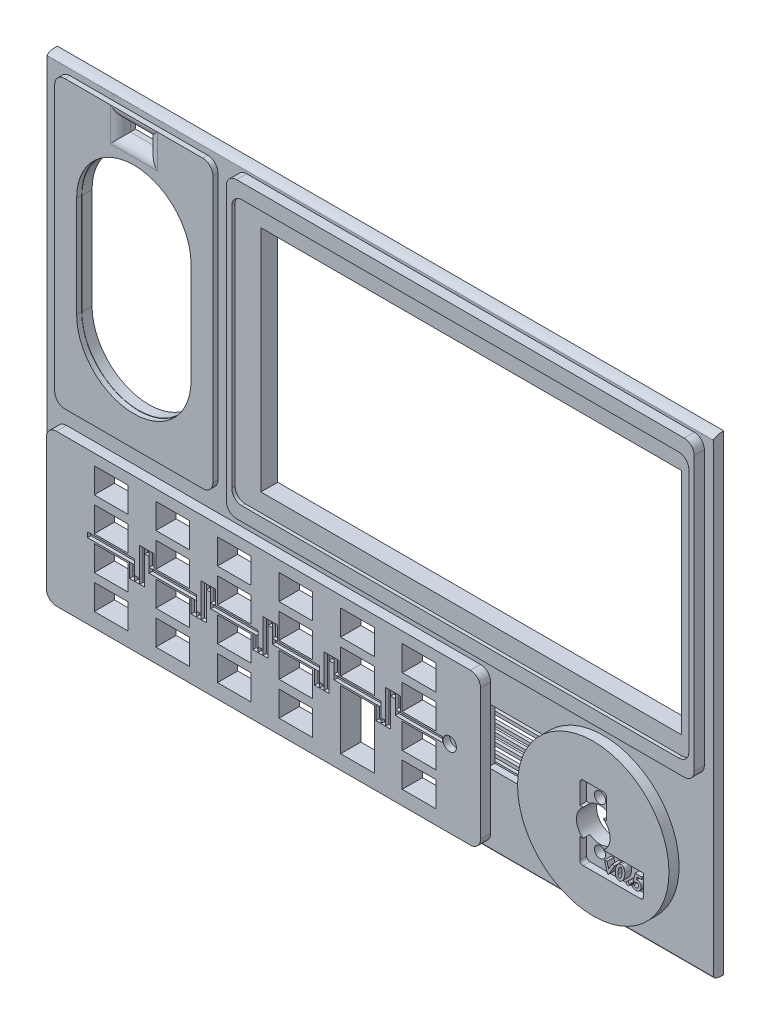
SolidWorks part; units mm, degrees
ref_plane "Front Plane" through (0, 0, 0) normal (0, 0, 1) x (1, 0, 0)
ref_plane "Top Plane" through (0, 0, 0) normal (0, 1, 0) x (1, 0, 0)
ref_plane "Right Plane" through (0, 0, 0) normal (1, 0, 0) x (0, 0, -1)
sketch "Sketch1" plane through (0, 0, 0) normal (0, 0, 1) x (1, 0, 0)
  line L1 (99, -70) -> (-99, -70)
  line L2 (99, -70) -> (99, 70)
  line L3 (99, 70) -> (-99, 70)
  line L4 (-99, -70) -> (-99, 70)
  line L5 (99, -70) -> (-99, 70) construction
  line L6 (99, 70) -> (-99, -70) construction
  point P0 (0, 0)
  dimension "D1" = 198
  dimension "D2" = 140
extrude "main_body" add sketch "Sketch1" along normal blind 3
fillet "long_corners" radius 3 2 edges at (0, 70, 3) (0, -70, 3) second distance 1 first distance on face at (0, 70, 1.5) first distance on face at (0, -70, 1.5)
sketch "Sketch2" plane through (0, 0, 3) normal (0, 0, 1) x (1, 0, 0)
  line L0 (-99, 24.75) -> (99, 24.75) construction
  line L1 (-99, 69) -> (-99, -69) construction
  line L2 (99, -69) -> (99, 69) construction
  line L3 (99, 69) -> (-99, 69) construction
  line L4 (-48.25, -17.75) -> (-95.25, -17.75)
  line L5 (-48.25, -17.75) -> (-48.25, 67.25)
  line L6 (-48.25, 67.25) -> (-95.25, 67.25)
  line L7 (-95.25, -17.75) -> (-95.25, 67.25)
  line L8 (-48.25, -17.75) -> (-95.25, 67.25) construction
  line L9 (-48.25, 67.25) -> (-95.25, -17.75) construction
  point P6 (-71.75, 24.75)
  dimension "D1" = 85
  dimension "D2" = 47
  dimension "D3" = 27.25
  dimension "D4" = 44.25
extrude "speaker" add sketch "Sketch2" along normal blind 1.5
fillet "speaker_corners" radius 3 4 edges at (-95.25, 67.25, 3.75) (-95.25, -17.75, 3.75) (-48.25, -17.75, 3.75) (-48.25, 67.25, 3.75)
sketch "Sketch19" plane through (0, 0, 4.5) normal (0, 0, 1) x (1, 0, 0)
  line L0 (-71.75, 67.25) -> (-71.75, -17.75) construction
  line L1 (-51.25, 67.25) -> (-92.25, 67.25) construction
  line L2 (-92.25, -17.75) -> (-51.25, -17.75) construction
  line L3 (-71.75, 8.25) -> (-71.75, 38.25) construction
  line L4 (-95.25, 64.25) -> (-95.25, -14.75) construction
  line L5 (-95.25, 24.75) -> (-48.25, 24.75) construction
  line L6 (-48.25, -14.75) -> (-48.25, 64.25) construction
  line L7 (-88.75, 8.25) -> (-88.75, 38.25)
  line L8 (-54.75, 8.25) -> (-54.75, 38.25)
  arc A0 (-88.75, 8.25) -> (-54.75, 8.25) centre (-71.75, 8.25) ccw
  arc A1 (-54.75, 38.25) -> (-88.75, 38.25) centre (-71.75, 38.25) ccw
  point P14 (-71.75, 23.25)
  point P19 (-71.75, -8.75)
  point P20 (-71.75, 55.25)
  dimension "D2" = 64
  dimension "D1" = 34
  dimension "D3" = 12
extrude "speaker_cut" cut sketch "Sketch19" against normal through all
sketch "Sketch21" plane through (0, 0, 0) normal (0, 0, -1) x (-1, 0, 0)
  line L0 (71.75, -8.75) -> (71.75, 55.25) construction
  line L2 (54.75, 8.25) -> (54.75, 38.25) construction
  line L3 (54.75, 23.25) -> (88.75, 23.25) construction
  line L4 (88.75, 38.25) -> (88.75, 8.25) construction
  line L5 (50.25, 59.25) -> (93.25, 59.25)
  line L6 (50.25, 59.25) -> (50.25, -12.75)
  line L7 (50.25, -12.75) -> (93.25, -12.75)
  line L8 (93.25, 59.25) -> (93.25, -12.75)
  line L9 (50.25, 59.25) -> (93.25, -12.75) construction
  line L10 (50.25, -12.75) -> (93.25, 59.25) construction
  arc A0 (54.75, 8.25) -> (88.75, 8.25) centre (71.75, 8.25) ccw construction
  arc A1 (88.75, 38.25) -> (54.75, 38.25) centre (71.75, 38.25) ccw construction
  point P14 (71.75, 23.25)
  dimension "D1" = 43
  dimension "D2" = 72
extrude "speaker_slot" cut sketch "Sketch21" against normal blind 3
sketch "Sketch36" plane through (0, 0, 3) normal (0, 0, -1) x (-1, 0, 0)
  line L0 (50.25, 23.25) -> (93.25, 23.25) construction
  line L1 (50.25, 59.25) -> (50.25, -12.75) construction
  line L2 (71.75, 8.2639) -> (71.75, 38.2361) construction
  line L3 (71.75, 8.2639) -> (71.75, 38.2361) construction
  line L4 (93.25, -12.75) -> (93.25, 59.25) construction
  line L5 (50.25, 59.25) -> (50.25, -12.75) construction
  line L6 (54.8316, 8.2639) -> (54.8316, 38.2361)
  line L9 (88.6684, 8.2639) -> (88.6684, 38.2361)
  line L10 (54.25, 8.2639) -> (54.25, 38.2361)
  line L11 (89.25, 8.2639) -> (89.25, 38.2361)
  line L12 (93.25, 59.25) -> (50.25, 59.25) construction
  line L13 (71.75, 59.25) -> (71.75, -12.75) construction
  line L14 (50.25, -12.75) -> (93.25, -12.75) construction
  line L23 (50.25, 57.25) -> (93.25, 57.25)
  line L25 (50.25, 57.25) -> (50.25, 56.75)
  line L26 (93.25, -0.25) -> (87.75, -0.25)
  line L27 (50.25, 56.75) -> (93.25, 56.75)
  line L28 (93.25, 57.25) -> (93.25, 56.75)
  line L37 (93.25, -12.75) -> (93.25, 59.25) construction
  line L38 (93.25, -0.25) -> (93.25, 0.25)
  line L39 (93.25, 0.25) -> (87.75, 0.25)
  line L48 (93.25, -10.75) -> (50.25, -10.75)
  line L49 (93.25, -10.75) -> (93.25, -10.25)
  line L50 (93.25, -10.25) -> (50.25, -10.25)
  line L51 (50.25, -10.75) -> (50.25, -10.25)
  line L52 (93.25, 46.75) -> (87.75, 46.75)
  line L53 (93.25, 46.75) -> (93.25, 46.25)
  line L54 (93.25, 46.25) -> (87.75, 46.25)
  line L55 (87.75, 46.75) -> (87.75, 46.25)
  line L56 (93.25, 35.25) -> (89.75, 35.25)
  line L57 (93.25, 35.25) -> (93.25, 34.75)
  line L58 (93.25, 34.75) -> (89.75, 34.75)
  line L59 (89.75, 35.25) -> (89.75, 34.75)
  line L60 (93.25, 23.25) -> (89.75, 23.25)
  line L61 (93.25, 23.25) -> (93.25, 23.75)
  line L62 (93.25, 23.75) -> (89.75, 23.75)
  line L63 (89.75, 23.25) -> (89.75, 23.75)
  line L64 (93.25, 10.75) -> (89.75, 10.75)
  line L65 (93.25, 10.75) -> (93.25, 11.25)
  line L66 (93.25, 11.25) -> (89.75, 11.25)
  line L67 (89.75, 10.75) -> (89.75, 11.25)
  line L68 (87.75, -0.25) -> (87.75, 0.25)
  line L69 (93.25, -5.25) -> (83.25, -5.25)
  line L70 (93.25, -5.25) -> (93.25, -5.75)
  line L71 (93.25, -5.75) -> (83.25, -5.75)
  line L72 (83.25, -5.25) -> (83.25, -5.75)
  line L73 (93.25, 52.25) -> (83.25, 52.25)
  line L74 (93.25, 52.25) -> (93.25, 51.75)
  line L75 (93.25, 51.75) -> (83.25, 51.75)
  line L76 (83.25, 52.25) -> (83.25, 51.75)
  line L77 (50.25, 52.25) -> (60.25, 52.25)
  line L78 (50.25, 52.25) -> (50.25, 51.75)
  line L79 (50.25, 51.75) -> (60.25, 51.75)
  line L80 (60.25, 52.25) -> (60.25, 51.75)
  line L81 (50.25, 46.75) -> (55.75, 46.75)
  line L82 (50.25, 46.75) -> (50.25, 46.25)
  line L83 (50.25, 46.25) -> (55.75, 46.25)
  line L84 (55.75, 46.75) -> (55.75, 46.25)
  line L85 (50.25, 35.25) -> (53.75, 35.25)
  line L86 (50.25, 35.25) -> (50.25, 34.75)
  line L87 (50.25, 34.75) -> (53.75, 34.75)
  line L88 (53.75, 35.25) -> (53.75, 34.75)
  line L89 (50.25, 23.25) -> (53.75, 23.25)
  line L90 (50.25, 23.25) -> (50.25, 23.75)
  line L91 (50.25, 23.75) -> (53.75, 23.75)
  line L92 (53.75, 23.25) -> (53.75, 23.75)
  line L93 (50.25, 10.25) -> (53.75, 10.25)
  line L94 (50.25, 10.25) -> (50.25, 10.75)
  line L95 (50.25, 10.75) -> (53.75, 10.75)
  line L96 (53.75, 10.25) -> (53.75, 10.75)
  line L97 (50.25, -0.25) -> (55.75, -0.25)
  line L98 (50.25, -0.25) -> (50.25, 0.25)
  line L99 (50.25, 0.25) -> (55.75, 0.25)
  line L100 (55.75, -0.25) -> (55.75, 0.25)
  line L101 (50.25, -5.25) -> (60.25, -5.25)
  line L102 (50.25, -5.25) -> (50.25, -5.75)
  line L103 (50.25, -5.75) -> (60.25, -5.75)
  line L104 (60.25, -5.25) -> (60.25, -5.75)
  arc A0 (54.25, 8.2639) -> (89.25, 8.2639) centre (71.75, 8.2639) ccw
  arc A1 (89.25, 38.2361) -> (54.25, 38.2361) centre (71.75, 38.2361) ccw
  arc A4 (54.8316, 8.2639) -> (88.6684, 8.2639) centre (71.75, 8.2639) ccw
  arc A5 (88.6684, 38.2361) -> (54.8316, 38.2361) centre (71.75, 38.2361) ccw
  point P6 (71.75, 23.25)
  point P22 (71.75, 23.25)
  point P31 (89.25, 23.25)
  point P32 (71.75, 55.1546)
  point P33 (71.75, -8.6546)
  point P95 (52, 35.25)
  point P96 (55.25, 51.75)
  point P97 (91.5, 10.75)
  dimension "D48" = 0.5816
  dimension "D1" = 33.8368
  dimension "D2" = 35
  dimension "D3" = 63.8091
  dimension "D4" = 0.5
  dimension "D5" = 0.5
  dimension "D6" = 0.5
  dimension "D7" = 0.5
  dimension "D8" = 0.5
  dimension "D9" = 11
  dimension "D10" = 11
  dimension "D11" = 5
  dimension "D12" = 4.5
  dimension "D13" = 10
  dimension "D14" = 5.5
  dimension "D15" = 3.5
  dimension "D16" = 3.5
  dimension "D17" = 0.5
  dimension "D18" = 0.5
  dimension "D19" = 0.5
  dimension "D20" = 0.5
  dimension "D21" = 11
  dimension "D22" = 11
  dimension "D23" = 5
  dimension "D24" = 10
  dimension "D25" = 5.5
  dimension "D26" = 3.5
  dimension "D27" = 3.5
  dimension "D28" = 0.5
  dimension "D29" = 0.5
  dimension "D30" = 0.5
  dimension "D31" = 0.5
  dimension "D32" = 0.5
  dimension "D33" = 0.5
  dimension "D34" = 0.5
  dimension "D35" = 12
  dimension "D36" = 10.5
  dimension "D37" = 5.5
  dimension "D38" = 5
  dimension "D39" = 4.5
  dimension "D40" = 3.5
  dimension "D41" = 10
  dimension "D42" = 4.5
  dimension "D43" = 5
  dimension "D44" = 10
  dimension "D45" = 3.5
  dimension "D46" = 5.5
  dimension "D47" = 10
extrude "speaker_print_support" add sketch "Sketch36" along normal blind 3
sketch "Sketch3" plane through (0, 0, 3) normal (0, 0, 1) x (1, 0, 0)
  line L0 (-99, 24.625) -> (99, 24.625) construction
  line L1 (-99, 69) -> (-99, -69) construction
  line L2 (99, -69) -> (99, 69) construction
  line L4 (-48.25, -14.75) -> (-48.25, 64.25) construction
  line L5 (96.25, -19) -> (-42.75, -19)
  line L6 (96.25, -19) -> (96.25, 68.25)
  line L7 (96.25, 68.25) -> (-42.75, 68.25)
  line L8 (-42.75, -19) -> (-42.75, 68.25)
  line L9 (96.25, -19) -> (-42.75, 68.25) construction
  line L10 (96.25, 68.25) -> (-42.75, -19) construction
  line L11 (99, 70) -> (-99, 70) construction
  point P8 (26.75, 24.625)
  dimension "D1" = 1.75
  dimension "D2" = 87.25
  dimension "D3" = 139
  dimension "D4" = 2.75
  dimension "D5" = 5.5
extrude "lcd" add sketch "Sketch3" along normal blind 3
fillet "lcd_corners" radius 3 4 edges at (96.25, -19, 4.5) (-42.75, -19, 4.5) (96.25, 68.25, 4.5) (-42.75, 68.25, 4.5)
sketch "Sketch9" plane through (0, 0, 6) normal (0, 0, 1) x (1, 0, 0)
  line L0 (-42.75, 24.5) -> (96.25, 24.5) construction
  line L1 (-42.75, 65.25) -> (-42.75, -16) construction
  line L2 (96.25, -16) -> (96.25, 65.25) construction
  line L3 (-39.75, -19) -> (93.25, -19) construction
  line L4 (94.65, -14.875) -> (-41.15, -14.875)
  line L5 (94.65, -14.875) -> (94.65, 63.875)
  line L6 (94.65, 63.875) -> (-41.15, 63.875)
  line L7 (-41.15, -14.875) -> (-41.15, 63.875)
  line L8 (94.65, -14.875) -> (-41.15, 63.875) construction
  line L9 (94.65, 63.875) -> (-41.15, -14.875) construction
  line L10 (93.25, 68.25) -> (-39.75, 68.25) construction
  line L11 (96.25, -16) -> (96.25, 65.25) construction
  point P6 (26.75, 24.5)
  dimension "D1" = 135.8
  dimension "D2" = 78.75
  dimension "D3" = 1.6
  dimension "D4" = 4.125
  dimension "D5" = 4.375
  dimension "D6" = 1.6
extrude "lcd_front" cut sketch "Sketch9" against normal blind 1
fillet "lcd_front_corners" radius 3 4 edges at (94.65, -14.875, 5.5) (94.65, 63.875, 5.5) (-41.15, 63.875, 5.5) (-41.15, -14.875, 5.5)
sketch "Sketch10" plane through (0, 0, 0) normal (0, 0, -1) x (-1, 0, 0)
  line L0 (-94.65, -11.875) -> (-94.65, 60.875) construction
  line L1 (-91.65, 63.875) -> (38.15, 63.875) construction
  line L2 (41.15, 63.875) -> (41.15, -14.875) construction
  line L3 (-94.65, 63.875) -> (41.15, 63.875) construction
  line L4 (33.5, -9.5) -> (-91.5, -9.5)
  line L5 (33.5, -9.5) -> (33.5, 58.5)
  line L6 (33.5, 58.5) -> (-91.5, 58.5)
  line L7 (-91.5, -9.5) -> (-91.5, 58.5)
  line L8 (-91.5, -9.5) -> (33.5, 58.5) construction
  line L9 (-91.5, 58.5) -> (33.5, -9.5) construction
  line L10 (-99, -70) -> (-99, 70) construction
  line L11 (-99, 70) -> (99, 70) construction
  line L13 (38.15, -14.875) -> (-91.65, -14.875) construction
  dimension "D1" = 125
  dimension "D2" = 68
  dimension "D3" = 7.5
  dimension "D4" = 7.65
  dimension "D5" = 11.5
  dimension "D6" = 5.375
  dimension "D7" = 3.15
  dimension "D8" = 5.375
  dimension "D9" = 5.375
extrude "lcd_back" cut sketch "Sketch10" against normal through all
sketch "Sketch4" plane through (0, 0, 3) normal (0, 0, 1) x (1, 0, 0)
  line L0 (-99, -45.75) -> (99, -45.75) construction
  line L1 (-99, 69) -> (-99, -69) construction
  line L2 (99, -69) -> (99, 69) construction
  line L4 (-92.25, -17.75) -> (-51.25, -17.75) construction
  line L5 (32.75, -68.25) -> (-96.25, -68.25)
  line L6 (32.75, -68.25) -> (32.75, -23.25)
  line L7 (32.75, -23.25) -> (-96.25, -23.25)
  line L8 (-96.25, -68.25) -> (-96.25, -23.25)
  line L9 (32.75, -68.25) -> (-96.25, -23.25) construction
  line L10 (32.75, -23.25) -> (-96.25, -68.25) construction
  line L11 (-99, -70) -> (99, -70) construction
  point P8 (-31.75, -45.75)
  dimension "D1" = 1.75
  dimension "D2" = 129
  dimension "D3" = 45
  dimension "D4" = 2.75
  dimension "D5" = 5.5
extrude "keypad" add sketch "Sketch4" along normal blind 3
fillet "keypad_corners" radius 3 4 edges at (-96.25, -68.25, 4.5) (32.75, -68.25, 4.5) (32.75, -23.25, 4.5) (-96.25, -23.25, 4.5)
sketch "Sketch25" plane through (0, 0, 6) normal (0, 0, 1) x (1, 0, 0)
  line L0 (-96.25, -30.25) -> (32.75, -30.25) construction
  line L1 (29.75, -23.25) -> (-93.25, -23.25) construction
  line L2 (-93.25, -68.25) -> (29.75, -68.25) construction
  line L3 (-77, -23.25) -> (-77, -68.25) construction
  line L5 (-35.4, -64) -> (32.75, -64) construction
  line L6 (-96.25, -26.25) -> (-96.25, -65.25) construction
  line L11 (32.75, -65.25) -> (32.75, -26.25) construction
  line L12 (-58.7, -23.25) -> (-58.7, -68.25) construction
  line L13 (-96.25, -40.25) -> (32.75, -40.25) construction
  line L14 (29.75, -23.25) -> (-93.25, -23.25) construction
  line L15 (-40.4, -23.25) -> (-40.4, -68.25) construction
  line L16 (-93.25, -68.25) -> (29.75, -68.25) construction
  line L17 (-72, -34) -> (-82, -34)
  line L18 (-22.1, -23.25) -> (-22.1, -68.25) construction
  line L19 (-96.25, -50.25) -> (32.75, -50.25) construction
  line L20 (-3.8, -23.25) -> (-3.8, -68.25) construction
  line L21 (-72, -34) -> (-72, -26.5)
  line L22 (14.5, -23.25) -> (14.5, -68.25) construction
  line L23 (-96.25, -26.25) -> (-96.25, -65.25) construction
  line L24 (-96.25, -60.25) -> (32.75, -60.25) construction
  line L25 (-72, -26.5) -> (-82, -26.5)
  line L26 (-82, -34) -> (-82, -26.5)
  line L27 (-72, -34) -> (-82, -26.5) construction
  line L28 (-72, -26.5) -> (-82, -34) construction
  line L29 (-72, -44) -> (-82, -44)
  line L30 (-72, -44) -> (-72, -36.5)
  line L31 (-72, -36.5) -> (-82, -36.5)
  line L32 (-82, -44) -> (-82, -36.5)
  line L33 (-72, -44) -> (-82, -36.5) construction
  line L34 (-72, -36.5) -> (-82, -44) construction
  line L35 (-72, -54) -> (-82, -54)
  line L36 (-72, -54) -> (-72, -46.5)
  line L37 (-72, -46.5) -> (-82, -46.5)
  line L38 (-82, -54) -> (-82, -46.5)
  line L39 (-72, -54) -> (-82, -46.5) construction
  line L40 (-72, -46.5) -> (-82, -54) construction
  line L41 (-72, -64) -> (-82, -64)
  line L42 (-72, -64) -> (-72, -56.5)
  line L43 (-72, -56.5) -> (-82, -56.5)
  line L44 (-82, -64) -> (-82, -56.5)
  line L45 (-72, -64) -> (-82, -56.5) construction
  line L46 (-72, -56.5) -> (-82, -64) construction
  line L47 (-53.7, -34) -> (-63.7, -34)
  line L48 (-53.7, -34) -> (-53.7, -26.5)
  line L49 (-53.7, -26.5) -> (-63.7, -26.5)
  line L50 (-63.7, -34) -> (-63.7, -26.5)
  line L51 (-53.7, -34) -> (-63.7, -26.5) construction
  line L52 (-53.7, -26.5) -> (-63.7, -34) construction
  line L53 (-53.7, -44) -> (-63.7, -44)
  line L54 (-53.7, -44) -> (-53.7, -36.5)
  line L55 (-53.7, -36.5) -> (-63.7, -36.5)
  line L56 (-63.7, -44) -> (-63.7, -36.5)
  line L57 (-53.7, -44) -> (-63.7, -36.5) construction
  line L58 (-53.7, -36.5) -> (-63.7, -44) construction
  line L59 (-53.7, -54) -> (-63.7, -54)
  line L60 (-53.7, -54) -> (-53.7, -46.5)
  line L61 (-53.7, -46.5) -> (-63.7, -46.5)
  line L62 (-63.7, -54) -> (-63.7, -46.5)
  line L63 (-53.7, -54) -> (-63.7, -46.5) construction
  line L64 (-53.7, -46.5) -> (-63.7, -54) construction
  line L65 (-53.7, -64) -> (-63.7, -64)
  line L66 (-53.7, -64) -> (-53.7, -56.5)
  line L67 (-53.7, -56.5) -> (-63.7, -56.5)
  line L68 (-63.7, -64) -> (-63.7, -56.5)
  line L69 (-53.7, -64) -> (-63.7, -56.5) construction
  line L70 (-53.7, -56.5) -> (-63.7, -64) construction
  line L71 (-35.4, -34) -> (-45.4, -34)
  line L72 (-35.4, -34) -> (-35.4, -26.5)
  line L73 (-35.4, -26.5) -> (-45.4, -26.5)
  line L74 (-45.4, -34) -> (-45.4, -26.5)
  line L75 (-35.4, -34) -> (-45.4, -26.5) construction
  line L76 (-35.4, -26.5) -> (-45.4, -34) construction
  line L77 (-35.4, -44) -> (-45.4, -44)
  line L78 (-35.4, -44) -> (-35.4, -36.5)
  line L79 (-35.4, -36.5) -> (-45.4, -36.5)
  line L80 (-45.4, -44) -> (-45.4, -36.5)
  line L81 (-35.4, -44) -> (-45.4, -36.5) construction
  line L82 (-35.4, -36.5) -> (-45.4, -44) construction
  line L83 (-35.4, -54) -> (-45.4, -54)
  line L84 (-35.4, -54) -> (-35.4, -46.5)
  line L85 (-35.4, -46.5) -> (-45.4, -46.5)
  line L86 (-45.4, -54) -> (-45.4, -46.5)
  line L87 (-35.4, -54) -> (-45.4, -46.5) construction
  line L88 (-35.4, -46.5) -> (-45.4, -54) construction
  line L89 (-35.4, -64) -> (-45.4, -64)
  line L90 (-35.4, -64) -> (-35.4, -56.5)
  line L91 (-35.4, -56.5) -> (-45.4, -56.5)
  line L92 (-45.4, -64) -> (-45.4, -56.5)
  line L93 (-35.4, -64) -> (-45.4, -56.5) construction
  line L94 (-35.4, -56.5) -> (-45.4, -64) construction
  line L95 (-17.1, -34) -> (-27.1, -34)
  line L96 (-17.1, -34) -> (-17.1, -26.5)
  line L97 (-17.1, -26.5) -> (-27.1, -26.5)
  line L98 (-27.1, -34) -> (-27.1, -26.5)
  line L99 (-17.1, -34) -> (-27.1, -26.5) construction
  line L100 (-17.1, -26.5) -> (-27.1, -34) construction
  line L101 (-17.1, -44) -> (-27.1, -44)
  line L102 (-17.1, -44) -> (-17.1, -36.5)
  line L103 (-17.1, -36.5) -> (-27.1, -36.5)
  line L104 (-27.1, -44) -> (-27.1, -36.5)
  line L105 (-17.1, -44) -> (-27.1, -36.5) construction
  line L106 (-17.1, -36.5) -> (-27.1, -44) construction
  line L111 (-17.1, -54) -> (-27.1, -54)
  line L112 (-17.1, -54) -> (-17.1, -46.5)
  line L113 (-17.1, -46.5) -> (-27.1, -46.5)
  line L114 (-27.1, -54) -> (-27.1, -46.5)
  line L115 (-17.1, -54) -> (-27.1, -46.5) construction
  line L116 (-17.1, -46.5) -> (-27.1, -54) construction
  line L117 (-17.1, -64) -> (-27.1, -64)
  line L118 (-17.1, -64) -> (-17.1, -56.5)
  line L119 (-17.1, -56.5) -> (-27.1, -56.5)
  line L120 (-27.1, -64) -> (-27.1, -56.5)
  line L121 (-17.1, -64) -> (-27.1, -56.5) construction
  line L122 (-17.1, -56.5) -> (-27.1, -64) construction
  line L127 (1.2, -34) -> (-8.8, -34)
  line L128 (1.2, -34) -> (1.2, -26.5)
  line L129 (1.2, -26.5) -> (-8.8, -26.5)
  line L130 (-8.8, -34) -> (-8.8, -26.5)
  line L131 (1.2, -34) -> (-8.8, -26.5) construction
  line L132 (1.2, -26.5) -> (-8.8, -34) construction
  line L133 (19.5, -34) -> (9.5, -34)
  line L134 (19.5, -34) -> (19.5, -26.5)
  line L135 (19.5, -26.5) -> (9.5, -26.5)
  line L136 (9.5, -34) -> (9.5, -26.5)
  line L137 (19.5, -34) -> (9.5, -26.5) construction
  line L138 (19.5, -26.5) -> (9.5, -34) construction
  line L139 (1.2, -44) -> (-8.8, -44)
  line L140 (1.2, -44) -> (1.2, -36.5)
  line L141 (1.2, -36.5) -> (-8.8, -36.5)
  line L142 (-8.8, -44) -> (-8.8, -36.5)
  line L143 (1.2, -44) -> (-8.8, -36.5) construction
  line L144 (1.2, -36.5) -> (-8.8, -44) construction
  line L145 (19.5, -44) -> (9.5, -44)
  line L146 (19.5, -44) -> (19.5, -36.5)
  line L147 (19.5, -36.5) -> (9.5, -36.5)
  line L148 (9.5, -44) -> (9.5, -36.5)
  line L149 (19.5, -44) -> (9.5, -36.5) construction
  line L150 (19.5, -36.5) -> (9.5, -44) construction
  line L151 (19.5, -54) -> (9.5, -54)
  line L152 (19.5, -54) -> (19.5, -46.5)
  line L153 (19.5, -46.5) -> (9.5, -46.5)
  line L154 (9.5, -54) -> (9.5, -46.5)
  line L155 (19.5, -54) -> (9.5, -46.5) construction
  line L156 (19.5, -46.5) -> (9.5, -54) construction
  line L157 (19.5, -64) -> (9.5, -64)
  line L158 (19.5, -64) -> (19.5, -56.5)
  line L159 (19.5, -56.5) -> (9.5, -56.5)
  line L160 (9.5, -64) -> (9.5, -56.5)
  line L161 (19.5, -64) -> (9.5, -56.5) construction
  line L162 (19.5, -56.5) -> (9.5, -64) construction
  line L163 (1.2, -64) -> (-8.8, -64)
  line L164 (1.2, -64) -> (1.2, -46.5)
  line L165 (1.2, -46.5) -> (-8.8, -46.5)
  line L166 (-8.8, -64) -> (-8.8, -46.5)
  line L167 (1.2, -64) -> (-8.8, -46.5) construction
  line L168 (1.2, -46.5) -> (-8.8, -64) construction
  point P34 (-77, -30.25)
  point P39 (-77, -40.25)
  point P44 (-77, -50.25)
  point P49 (-77, -60.25)
  point P54 (-58.7, -30.25)
  point P59 (-58.7, -40.25)
  point P64 (-58.7, -50.25)
  point P69 (-58.7, -60.25)
  point P74 (-40.4, -30.25)
  point P79 (-40.4, -40.25)
  point P84 (-40.4, -50.25)
  point P89 (-40.4, -60.25)
  point P94 (-22.1, -30.25)
  point P99 (-22.1, -40.25)
  point P104 (-22.1, -50.25)
  point P109 (-22.1, -60.25)
  point P114 (-3.8, -30.25)
  point P119 (14.5, -30.25)
  point P124 (-3.8, -40.25)
  point P129 (14.5, -40.25)
  point P134 (14.5, -50.25)
  point P139 (14.5, -60.25)
  point P144 (-3.8, -55.25)
  dimension "D1" = 18.25
  dimension "D2" = 18.3
  dimension "D3" = 18.3
  dimension "D4" = 18.3
  dimension "D5" = 18.3
  dimension "D6" = 18.3
  dimension "D7" = 19.25
  dimension "D8" = 7
  dimension "D9" = 10
  dimension "D10" = 10
  dimension "D11" = 10
  dimension "D12" = 8
  dimension "D13" = 10
  dimension "D14" = 10
  dimension "D15" = 10
  dimension "D16" = 10
  dimension "D17" = 10
  dimension "D18" = 10
  dimension "D19" = 10
  dimension "D20" = 10
  dimension "D21" = 10
  dimension "D22" = 10
  dimension "D23" = 10
  dimension "D24" = 10
  dimension "D25" = 10
  dimension "D26" = 10
  dimension "D27" = 10
  dimension "D28" = 10
  dimension "D29" = 10
  dimension "D30" = 10
  dimension "D31" = 10
  dimension "D32" = 10
  dimension "D33" = 10
  dimension "D34" = 10
  dimension "D35" = 10
  dimension "D36" = 7.5
  dimension "D37" = 7.5
  dimension "D38" = 7.5
  dimension "D39" = 7.5
  dimension "D40" = 7.5
  dimension "D41" = 7.5
  dimension "D42" = 17.5
  dimension "D43" = 7.5
  dimension "D44" = 7.5
  dimension "D45" = 7.5
  dimension "D46" = 7.5
  dimension "D47" = 7.5
  dimension "D48" = 7.5
  dimension "D49" = 7.5
  dimension "D50" = 7.5
  dimension "D51" = 7.5
  dimension "D52" = 7.5
  dimension "D53" = 7.5
  dimension "D54" = 7.5
  dimension "D55" = 7.5
  dimension "D56" = 7.5
  dimension "D57" = 7.5
  dimension "D58" = 7.5
  dimension "D59" = 5
extrude "keypad_cuts_0.8" cut sketch "Sketch25" against normal through all
sketch "Sketch40" plane through (0, 0, 6) normal (0, 0, 1) x (1, 0, 0)
  line L0 (16.75, -23.25) -> (16.75, -68.25) construction
  line L1 (-8.25, -23.25) -> (-8.25, -68.25) construction
  line L2 (-67.25, -23.25) -> (-67.25, -68.25) construction
  line L3 (-96.25, -45.75) -> (32.75, -45.75) construction
  line L4 (-83.25, -23.25) -> (-83.25, -68.25) construction
  line L5 (29.75, -23.25) -> (-93.25, -23.25) construction
  line L6 (-93.25, -68.25) -> (29.75, -68.25) construction
  line L11 (-77.25, -49.75) -> (-89.25, -49.75)
  line L12 (-77.25, -49.75) -> (-77.25, -41.75)
  line L13 (-93.25, -68.25) -> (29.75, -68.25) construction
  line L14 (-77.25, -41.75) -> (-89.25, -41.75)
  line L15 (-89.25, -49.75) -> (-89.25, -41.75)
  line L16 (-35.25, -68.25) -> (-35.25, -23.25) construction
  line L18 (29.75, -23.25) -> (-93.25, -23.25) construction
  line L19 (-77.25, -49.75) -> (-89.25, -41.75) construction
  line L20 (-51.25, -68.25) -> (-51.25, -23.25) construction
  line L22 (-77.25, -41.75) -> (-89.25, -49.75) construction
  line L23 (-61.25, -49.75) -> (-73.25, -49.75)
  line L24 (-61.25, -49.75) -> (-61.25, -41.75)
  line L25 (-61.25, -41.75) -> (-73.25, -41.75)
  line L26 (-73.25, -49.75) -> (-73.25, -41.75)
  line L27 (-61.25, -49.75) -> (-73.25, -41.75) construction
  line L28 (-61.25, -41.75) -> (-73.25, -49.75) construction
  line L29 (-45.25, -49.75) -> (-57.25, -49.75)
  line L30 (-45.25, -49.75) -> (-45.25, -41.75)
  line L31 (-45.25, -41.75) -> (-57.25, -41.75)
  line L32 (-57.25, -49.75) -> (-57.25, -41.75)
  line L33 (-45.25, -49.75) -> (-57.25, -41.75) construction
  line L34 (-45.25, -41.75) -> (-57.25, -49.75) construction
  line L35 (-29.25, -49.75) -> (-41.25, -49.75)
  line L36 (-29.25, -49.75) -> (-29.25, -41.75)
  line L37 (-29.25, -41.75) -> (-41.25, -41.75)
  line L38 (-41.25, -49.75) -> (-41.25, -41.75)
  line L39 (-29.25, -49.75) -> (-41.25, -41.75) construction
  line L40 (-29.25, -41.75) -> (-41.25, -49.75) construction
  line L45 (-2.25, -41.75) -> (-14.25, -41.75)
  line L46 (-2.25, -41.75) -> (-2.25, -33.75)
  line L51 (-2.25, -33.75) -> (-14.25, -33.75)
  line L52 (-14.25, -41.75) -> (-14.25, -33.75)
  line L53 (22.75, -35.75) -> (10.75, -35.75)
  line L54 (22.75, -35.75) -> (22.75, -27.75)
  line L55 (22.75, -27.75) -> (10.75, -27.75)
  line L56 (10.75, -35.75) -> (10.75, -27.75)
  line L57 (22.75, -35.75) -> (10.75, -27.75) construction
  line L58 (22.75, -27.75) -> (10.75, -35.75) construction
  line L59 (22.75, -63.75) -> (10.75, -63.75)
  line L60 (22.75, -63.75) -> (22.75, -55.75)
  line L61 (22.75, -55.75) -> (10.75, -55.75)
  line L62 (10.75, -63.75) -> (10.75, -55.75)
  line L63 (22.75, -63.75) -> (10.75, -55.75) construction
  line L64 (22.75, -55.75) -> (10.75, -63.75) construction
  line L69 (32.75, -65.25) -> (32.75, -26.25) construction
  line L70 (-2.25, -57.25) -> (-14.25, -57.25)
  line L75 (-2.25, -57.25) -> (-2.25, -49.25)
  line L76 (-2.25, -49.25) -> (-14.25, -49.25)
  line L77 (-2.25, -41.75) -> (-14.25, -33.75) construction
  line L78 (-2.25, -33.75) -> (-14.25, -41.75) construction
  line L85 (-14.25, -57.25) -> (-14.25, -49.25)
  line L86 (-2.25, -57.25) -> (-14.25, -49.25) construction
  line L87 (-2.25, -49.25) -> (-14.25, -57.25) construction
  line L88 (-96.25, -26.25) -> (-96.25, -65.25) construction
  line L89 (32.75, -65.25) -> (32.75, -26.25) construction
  line L93 (32.75, -59.75) -> (-96.25, -59.75) construction
  line L94 (-96.25, -31.75) -> (32.75, -31.75) construction
  line L95 (32.75, -31.75) -> (32.75, -37.75) construction
  line L96 (32.75, -37.75) -> (-96.25, -37.75) construction
  line L99 (-96.25, -26.25) -> (-96.25, -65.25) construction
  line L100 (-96.25, -53.75) -> (32.75, -53.75) construction
  point P18 (-83.25, -45.75)
  point P25 (-67.25, -45.75)
  point P30 (-51.25, -45.75)
  point P35 (-35.25, -45.75)
  point P40 (-8.25, -37.75)
  point P45 (-8.25, -53.25)
  point P50 (16.75, -31.75)
  point P55 (16.75, -59.75)
  dimension "D1" = 8
  dimension "D2" = 8
  dimension "D3" = 8
  dimension "D4" = 8
  dimension "D5" = 8
  dimension "D6" = 12
  dimension "D7" = 8
  dimension "D8" = 8
  dimension "D9" = 12
  dimension "D10" = 12
  dimension "D11" = 12
  dimension "D12" = 12
  dimension "D13" = 12
  dimension "D14" = 12
  dimension "D15" = 8
  dimension "D16" = 12
  dimension "D17" = 8
  dimension "D18" = 8
  dimension "D19" = 27
  dimension "D20" = 14
  dimension "D21" = 16
  dimension "D22" = 16
  dimension "D23" = 16
  dimension "D24" = 25
  dimension "D25" = 14
extrude "keypad_cuts_0.7" [suppressed] cut sketch "Sketch40" against normal through all
sketch "Sketch41" [suppressed] plane through (0, 0, 0) normal (0, 0, -1) x (-1, 0, 0)
  line L0 (-22.75, -27.75) -> (-10.75, -35.75) construction
  line L1 (-22.75, -55.75) -> (-10.75, -63.75) construction
  line L2 (8.25, -33.75) -> (8.25, -57.25) construction
  line L3 (-10.75, -63.75) -> (-22.75, -63.75) construction
  line L4 (29.25, -45.75) -> (89.25, -45.75) construction
  line L5 (29.25, -49.75) -> (29.25, -41.75) construction
  line L6 (89.25, -41.75) -> (89.25, -49.75) construction
  line L7 (-6.75, -39.75) -> (-26.75, -39.75)
  line L8 (2.25, -33.75) -> (14.25, -33.75) construction
  line L9 (-6.75, -39.75) -> (-6.75, -23.75)
  line L10 (91.25, -52.75) -> (27.25, -52.75)
  line L11 (-6.75, -23.75) -> (-26.75, -23.75)
  line L12 (14.25, -57.25) -> (2.25, -57.25) construction
  line L13 (-26.75, -39.75) -> (-26.75, -23.75)
  line L14 (-10.75, -55.75) -> (-22.75, -63.75) construction
  line L15 (-6.75, -39.75) -> (-26.75, -23.75) construction
  line L16 (-10.75, -35.75) -> (-22.75, -35.75) construction
  line L17 (-22.75, -35.75) -> (-22.75, -27.75) construction
  line L18 (-22.75, -35.75) -> (-10.75, -27.75) construction
  line L19 (-6.75, -23.75) -> (-26.75, -39.75) construction
  line L21 (-6.75, -67.75) -> (-26.75, -67.75)
  line L22 (16.25, -59.5) -> (0.25, -59.5)
  line L23 (-6.75, -67.75) -> (-6.75, -51.75)
  line L24 (91.25, -52.75) -> (91.25, -38.75)
  line L25 (-6.75, -51.75) -> (-26.75, -51.75)
  line L26 (91.25, -38.75) -> (27.25, -38.75)
  line L27 (-26.75, -67.75) -> (-26.75, -51.75)
  line L28 (27.25, -52.75) -> (27.25, -38.75)
  line L29 (-6.75, -67.75) -> (-26.75, -51.75) construction
  line L30 (91.25, -52.75) -> (27.25, -38.75) construction
  line L31 (-6.75, -51.75) -> (-26.75, -67.75) construction
  line L36 (16.25, -59.5) -> (16.25, -31.5)
  line L37 (16.25, -31.5) -> (0.25, -31.5)
  line L42 (0.25, -59.5) -> (0.25, -31.5)
  line L43 (16.25, -59.5) -> (0.25, -31.5) construction
  line L48 (91.25, -38.75) -> (27.25, -52.75) construction
  line L49 (16.25, -31.5) -> (0.25, -59.5) construction
  point P19 (59.25, -45.75)
  point P44 (8.25, -45.5)
  point P68 (-16.75, -59.75)
  point P69 (-16.75, -31.75)
  dimension "D1" = 20
  dimension "D2" = 20
  dimension "D3" = 16
  dimension "D4" = 16
  dimension "D5" = 16
  dimension "D6" = 28
  dimension "D7" = 64
  dimension "D8" = 14
extrude "keypad_back_0.7" [suppressed] cut sketch "Sketch41" against normal blind 5
sketch "Sketch5" plane through (0, 0, 3) normal (0, 0, 1) x (1, 0, 0)
  line L0 (32.75, -45.75) -> (99, -45.75) construction
  line L1 (32.75, -65.25) -> (32.75, -26.25) construction
  line L2 (99, -69) -> (99, 69) construction
  circle A0 centre (66.25, -45.75) radius 22.5
  dimension "D1" = 45
  dimension "D2" = 32.75
  dimension "D3" = 33.5
extrude "vfo" add sketch "Sketch5" along normal blind 3
sketch "Sketch7" plane through (0, 0, 6) normal (0, 0, 1) x (1, 0, 0)
  line L0 (43.75, -45.75) -> (88.75, -45.75) construction
  line L1 (66.25, -23.25) -> (66.25, -68.25) construction
  circle A0 centre (66.25, -45.75) radius 22.5 construction
  circle A1 centre (66.25, -45.75) radius 22.5 construction
  circle A2 centre (66.25, -45.75) radius 5
  dimension "D1" = 10
extrude "vfo_encoder_knob_cut" cut sketch "Sketch7" against normal through all
sketch "Sketch37" plane through (0, 0, 6) normal (0, 0, 1) x (1, 0, 0)
  line L1 (62.25, -49.75) -> (81.25, -49.75)
  line L2 (62.25, -49.75) -> (62.25, -56.75)
  line L3 (62.25, -56.75) -> (81.25, -56.75)
  line L4 (81.25, -49.75) -> (81.25, -56.75)
  line L5 (62.25, -34.75) -> (70.25, -34.75)
  line L6 (62.25, -34.75) -> (62.25, -41.75)
  line L7 (62.25, -41.75) -> (70.25, -41.75)
  line L8 (70.25, -34.75) -> (70.25, -41.75)
  circle A0 centre (66.25, -45.75) radius 5 construction
  dimension "D1" = 7
  dimension "D2" = 19
  dimension "D3" = 4
  dimension "D4" = 15
  dimension "D5" = 8
  dimension "D6" = 7
  dimension "D7" = 4
  dimension "D8" = 4
extrude "logo_cut" cut sketch "Sketch37" against normal blind 2
sketch "Sketch39" plane through (0, 0, 4) normal (0, 0, 1) x (1, 0, 0)
  line L0 (62.25, -49.75) -> (62.25, -56.75) construction
  line L1 (62.25, -56.75) -> (81.25, -56.75) construction
  text T0 " v0.5\r\n" font "Century Gothic" height in points 16
  dimension "D1" = 5.5
  dimension "D2" = 1.5336
extrude "logo_txt_ver" add sketch "Sketch39" along normal blind 2
fillet "logo_corners" radius 1 4 edges at (62.25, -34.75, 5) (70.25, -34.75, 5) (81.25, -56.75, 5) (62.25, -56.75, 5)
sketch "esp32" plane through (0, 0, 0) normal (0, 0, -1) x (-1, 0, 0)
  line L0 (99, -70) -> (-99, -70) construction
  line L1 (-50.5, -32.05) -> (-32, -32.05)
  line L2 (-50.5, -32.05) -> (-50.5, -48.55)
  line L3 (-50.5, -48.55) -> (-32, -48.55)
  line L4 (-32, -32.05) -> (-32, -48.55)
  line L5 (-99, -70) -> (-99, 70) construction
  dimension "D1" = 21.45
  dimension "D2" = 48.5
  dimension "D3" = 16.5
  dimension "D4" = 18.5
extrude "esp32_can_cut" cut sketch "esp32" against normal blind 3
sketch "Sketch43" plane through (0, 0, 0) normal (0, 0, -1) x (-1, 0, 0)
  line L0 (99, -70) -> (-99, -70) construction
  line L1 (-34, -50.5) -> (-50.5, -50.5)
  line L2 (-34, -50.5) -> (-34, -67)
  line L3 (-34, -67) -> (-50.5, -67)
  line L4 (-50.5, -50.5) -> (-50.5, -67)
  line L5 (-99, -70) -> (-99, 70) construction
  dimension "D1" = 16.5
  dimension "D2" = 16.5
  dimension "D3" = 3
  dimension "D4" = 48.5
extrude "lora_cut" cut sketch "Sketch43" against normal blind 2.5
fillet "rf_corners" [suppressed] radius 1
sketch "Sketch44" plane through (0, 0, 6) normal (0, 0, 1) x (1, 0, 0)
  line L0 (66.25, -23.25) -> (66.25, -68.25) construction
  line L1 (66.25, -37.1) -> (62.25, -37.1) construction
  line L2 (62.25, -35.75) -> (62.25, -41.75) construction
  line L4 (66.25, -54.4) -> (62.25, -54.4) construction
  line L5 (62.25, -49.75) -> (62.25, -55.75) construction
  arc A0 (43.9249, -48.55) -> (48.4018, -32.05) centre (66.25, -45.75) ccw construction
  circle A1 centre (66.25, -45.75) radius 22.5 construction
  circle A2 centre (66.25, -38.75) radius 1.65
  circle A3 centre (66.25, -52.75) radius 1.65
  dimension "D1" = 3.3
  dimension "D2" = 3.3
  dimension "D5" = 17.3
  dimension "D3" = 15.5
  dimension "D4" = 15.5
  dimension "D6" = 14
extrude "encoder_mount_holes" cut sketch "Sketch44" against normal through all
sketch "Sketch47" plane through (0, 0, 0) normal (0, 0, -1) x (-1, 0, 0)
  line L0 (-50.5, -48.55) -> (-32, -48.55) construction
  line L1 (-31, -49.55) -> (-58, -49.55)
  line L2 (-31, -49.55) -> (-31, -31.05)
  line L3 (-31, -31.05) -> (-58, -31.05)
  line L4 (-58, -49.55) -> (-58, -31.05)
  line L5 (-31, -49.55) -> (-58, -31.05) construction
  line L6 (-31, -31.05) -> (-58, -49.55) construction
  line L7 (-50.5, -32.05) -> (-50.5, -48.55) construction
  point P0 (-44.5, -40.3)
  dimension "D1" = 27
  dimension "D2" = 18.5
  dimension "D3" = 1
  dimension "D4" = 7.5
extrude "esp32_ex_cut" cut sketch "Sketch47" against normal blind 1
sketch "Sketch49" plane through (0, 0, 0) normal (0, 0, -1) x (-1, 0, 0)
  line L0 (71.75, 59.25) -> (71.75, 70) construction
  line L1 (93.25, 59.25) -> (50.25, 59.25) construction
  line L2 (-99, 70) -> (99, 70) construction
  line L4 (75.75, 60.25) -> (67.75, 60.25)
  line L5 (75.75, 60.25) -> (75.75, 64.25)
  line L6 (75.75, 64.25) -> (67.75, 64.25)
  line L7 (67.75, 60.25) -> (67.75, 64.25)
  line L8 (75.75, 60.25) -> (67.75, 64.25) construction
  line L9 (75.75, 64.25) -> (67.75, 60.25) construction
  point P6 (71.75, 62.25)
  dimension "D1" = 8
  dimension "D2" = 4
  dimension "D3" = 1
extrude "amb_sensor" cut sketch "Sketch49" against normal through all
fillet "amb_corners" radius 3 4 edges at (-67.75, 62.25, 4.5) (-71.75, 64.25, 4.5) (-75.75, 62.25, 4.5) (-71.75, 60.25, 4.5)
sketch "Sketch50" plane through (0, 0, 6) normal (0, 0, 1) x (1, 0, 0)
  line L0 (-96.25, -45.1902) -> (-96.25, -45.25) construction
  line L1 (-96.25, -26.25) -> (-96.25, -65.25) construction
  line L2 (-96.25, -40.25) -> (32.75, -40.25) construction
  line L3 (-67.75, -23.25) -> (-67.75, -68.25) construction
  line L4 (29.75, -23.25) -> (-93.25, -23.25) construction
  line L5 (-93.25, -68.25) -> (29.75, -68.25) construction
  line L6 (-31.25, -23.25) -> (-31.25, -68.25) construction
  line L7 (29.75, -23.25) -> (-93.25, -23.25) construction
  line L8 (-49.5, -23.25) -> (-49.5, -68.25) construction
  line L9 (5.25, -23.25) -> (5.25, -68.25) construction
  line L10 (-13, -23.25) -> (-13, -68.25) construction
  line L11 (-96.25, -26.25) -> (-96.25, -65.25) construction
  line L12 (-96.25, -45.25) -> (32.75, -45.25) construction
  line L13 (32.75, -65.25) -> (32.75, -26.25) construction
  line L14 (9.5, -36.5) -> (9.5, -44) construction
  line L15 (-70, -46) -> (-84, -46)
  line L16 (-70, -46) -> (-70, -44.5)
  line L17 (-70, -44.5) -> (-84, -44.5)
  line L18 (-84, -46) -> (-84, -44.5)
  line L19 (-70, -46) -> (-84, -44.5) construction
  line L20 (-70, -44.5) -> (-84, -46) construction
  line L21 (-51.7, -46) -> (-65.7, -46)
  line L22 (-51.7, -46) -> (-51.7, -44.5)
  line L23 (-51.7, -44.5) -> (-65.7, -44.5)
  line L24 (-65.7, -46) -> (-65.7, -44.5)
  line L25 (-51.7, -46) -> (-65.7, -44.5) construction
  line L26 (-51.7, -44.5) -> (-65.7, -46) construction
  line L27 (-33.4, -46) -> (-47.4, -46)
  line L28 (-33.4, -46) -> (-33.4, -44.5)
  line L29 (-33.4, -44.5) -> (-47.4, -44.5)
  line L30 (-47.4, -46) -> (-47.4, -44.5)
  line L31 (-33.4, -46) -> (-47.4, -44.5) construction
  line L32 (-33.4, -44.5) -> (-47.4, -46) construction
  line L33 (-15.1, -46) -> (-29.1, -46)
  line L34 (-15.1, -46) -> (-15.1, -44.5)
  line L35 (-15.1, -44.5) -> (-29.1, -44.5)
  line L36 (-29.1, -46) -> (-29.1, -44.5)
  line L37 (-15.1, -46) -> (-29.1, -44.5) construction
  line L38 (-15.1, -44.5) -> (-29.1, -46) construction
  line L39 (3.2, -46) -> (-10.8, -46)
  line L40 (3.2, -46) -> (3.2, -44.5)
  line L41 (3.2, -44.5) -> (-10.8, -44.5)
  line L42 (-10.8, -46) -> (-10.8, -44.5)
  line L43 (3.2, -46) -> (-10.8, -44.5) construction
  line L44 (3.2, -44.5) -> (-10.8, -46) construction
  line L45 (21.5, -46) -> (7.5, -46)
  line L46 (21.5, -46) -> (21.5, -44.5)
  line L47 (21.5, -44.5) -> (7.5, -44.5)
  line L48 (7.5, -46) -> (7.5, -44.5)
  line L49 (21.5, -46) -> (7.5, -44.5) construction
  line L50 (21.5, -44.5) -> (7.5, -46) construction
  line L51 (-8.8, -36.5) -> (-8.8, -44) construction
  line L52 (-27.1, -36.5) -> (-27.1, -44) construction
  line L53 (-45.4, -36.5) -> (-45.4, -44) construction
  line L54 (-63.7, -36.5) -> (-63.7, -44) construction
  line L55 (-82, -36.5) -> (-82, -44) construction
  line L56 (1.2, -64) -> (1.2, -46.5) construction
  line L57 (7.49, -40.25) -> (8.99, -40.25)
  line L58 (32.75, -65.25) -> (32.75, -48.55) construction
  line L59 (32.75, -50.25) -> (-96.25, -50.25) construction
  line L60 (7.49, -40.25) -> (7.49, -44.49)
  line L61 (7.49, -44.49) -> (8.99, -44.49)
  line L62 (8.99, -40.25) -> (8.99, -44.49)
  line L63 (3.2, -50.25) -> (1.7, -50.25)
  line L64 (3.2, -50.25) -> (3.2, -46.01)
  line L65 (3.2, -46.01) -> (1.7, -46.01)
  line L66 (1.7, -50.25) -> (1.7, -46.01)
  line L67 (4.52, -40.25) -> (6.02, -40.25)
  line L68 (4.52, -40.25) -> (4.52, -50.25)
  line L69 (4.52, -50.25) -> (6.02, -50.25)
  line L70 (6.02, -40.25) -> (6.02, -50.25)
  line L71 (3.21, -50.25) -> (4.51, -50.25)
  line L72 (3.21, -50.25) -> (3.21, -48.75)
  line L73 (3.21, -48.75) -> (4.51, -48.75)
  line L74 (4.51, -50.25) -> (4.51, -48.75)
  line L75 (6.03, -40.25) -> (7.48, -40.25)
  line L76 (6.03, -40.25) -> (6.03, -41.75)
  line L77 (6.03, -41.75) -> (7.48, -41.75)
  line L78 (7.48, -40.25) -> (7.48, -41.75)
  line L79 (-72, -54) -> (-72, -46.5) construction
  line L80 (-13.78, -40.25) -> (-12.28, -40.25)
  line L81 (-13.78, -40.25) -> (-13.78, -50.25)
  line L82 (-13.78, -50.25) -> (-12.28, -50.25)
  line L83 (-12.28, -40.25) -> (-12.28, -50.25)
  line L84 (-31.88, -40.25) -> (-30.38, -40.25)
  line L85 (-31.88, -40.25) -> (-31.88, -50.25)
  line L86 (-31.88, -50.25) -> (-30.38, -50.25)
  line L87 (-30.38, -40.25) -> (-30.38, -50.25)
  line L88 (-50.23, -40.25) -> (-48.73, -40.25)
  line L89 (-50.23, -40.25) -> (-50.23, -50.25)
  line L90 (-50.23, -50.25) -> (-48.73, -50.25)
  line L91 (-48.73, -40.25) -> (-48.73, -50.25)
  line L92 (-68.53, -40.25) -> (-67.03, -40.25)
  line L93 (-68.53, -40.25) -> (-68.53, -50.25)
  line L94 (-68.53, -50.25) -> (-67.03, -50.25)
  line L95 (-67.03, -40.25) -> (-67.03, -50.25)
  line L96 (-70, -46.01) -> (-71.5, -46.01)
  line L97 (-70, -46.01) -> (-70, -50.25)
  line L98 (-70, -50.25) -> (-71.5, -50.25)
  line L99 (-71.5, -46.01) -> (-71.5, -50.25)
  line L100 (-69.99, -50.25) -> (-68.54, -50.25)
  line L101 (-69.99, -50.25) -> (-69.99, -48.75)
  line L102 (-69.99, -48.75) -> (-68.54, -48.75)
  line L103 (-68.54, -50.25) -> (-68.54, -48.75)
  line L104 (-53.7, -54) -> (-53.7, -46.5) construction
  line L105 (-67.02, -40.25) -> (-65.72, -40.25)
  line L106 (-67.02, -40.25) -> (-67.02, -41.75)
  line L107 (-67.02, -41.75) -> (-65.72, -41.75)
  line L108 (-65.72, -40.25) -> (-65.72, -41.75)
  line L109 (-65.71, -40.25) -> (-64.21, -40.25)
  line L110 (-65.71, -40.25) -> (-65.71, -44.49)
  line L111 (-65.71, -44.49) -> (-64.21, -44.49)
  line L112 (-64.21, -40.25) -> (-64.21, -44.49)
  line L113 (-51.7, -46.01) -> (-53.2, -46.01)
  line L114 (-51.7, -46.01) -> (-51.7, -50.25)
  line L115 (-51.7, -50.25) -> (-53.2, -50.25)
  line L116 (-53.2, -46.01) -> (-53.2, -50.25)
  line L117 (-51.69, -50.25) -> (-50.24, -50.25)
  line L118 (-51.69, -50.25) -> (-51.69, -48.75)
  line L119 (-51.69, -48.75) -> (-50.24, -48.75)
  line L120 (-50.24, -50.25) -> (-50.24, -48.75)
  line L121 (-48.72, -40.25) -> (-47.42, -40.25)
  line L122 (-48.72, -40.25) -> (-48.72, -41.75)
  line L123 (-48.72, -41.75) -> (-47.42, -41.75)
  line L124 (-47.42, -40.25) -> (-47.42, -41.75)
  line L125 (-47.41, -40.25) -> (-45.91, -40.25)
  line L126 (-47.41, -40.25) -> (-47.41, -44.49)
  line L127 (-47.41, -44.49) -> (-45.91, -44.49)
  line L128 (-45.91, -40.25) -> (-45.91, -44.49)
  line L129 (-33.4, -46.01) -> (-34.9, -46.01)
  line L130 (-33.4, -46.01) -> (-33.4, -50.25)
  line L131 (-33.4, -50.25) -> (-34.9, -50.25)
  line L132 (-34.9, -46.01) -> (-34.9, -50.25)
  line L133 (-33.39, -50.25) -> (-31.89, -50.25)
  line L134 (-33.39, -50.25) -> (-33.39, -48.75)
  line L135 (-33.39, -48.75) -> (-31.89, -48.75)
  line L136 (-31.89, -50.25) -> (-31.89, -48.75)
  line L137 (-30.37, -40.25) -> (-29.11, -40.25)
  line L138 (-30.37, -40.25) -> (-30.37, -41.75)
  line L139 (-30.37, -41.75) -> (-29.11, -41.75)
  line L140 (-29.11, -40.25) -> (-29.11, -41.75)
  line L141 (-29.1, -40.25) -> (-27.6, -40.25)
  line L142 (-29.1, -40.25) -> (-29.1, -44.49)
  line L143 (-29.1, -44.49) -> (-27.6, -44.49)
  line L144 (-27.6, -40.25) -> (-27.6, -44.49)
  line L145 (-15.1, -46.01) -> (-16.6, -46.01)
  line L146 (-15.1, -46.01) -> (-15.1, -50.25)
  line L147 (-15.1, -50.25) -> (-16.6, -50.25)
  line L148 (-16.6, -46.01) -> (-16.6, -50.25)
  line L149 (-15.09, -50.25) -> (-13.79, -50.25)
  line L150 (-15.09, -50.25) -> (-15.09, -48.75)
  line L151 (-15.09, -48.75) -> (-13.79, -48.75)
  line L152 (-13.79, -50.25) -> (-13.79, -48.75)
  line L153 (-12.27, -40.25) -> (-10.81, -40.25)
  line L154 (-12.27, -40.25) -> (-12.27, -41.75)
  line L155 (-12.27, -41.75) -> (-10.81, -41.75)
  line L156 (-10.81, -40.25) -> (-10.81, -41.75)
  line L157 (-10.8, -40.25) -> (-9.3, -40.25)
  line L158 (-10.8, -40.25) -> (-10.8, -44.49)
  line L159 (-10.8, -44.49) -> (-9.3, -44.49)
  line L160 (-9.3, -40.25) -> (-9.3, -44.49)
  line L161 (-35.4, -54) -> (-35.4, -46.5) construction
  line L162 (-17.1, -54) -> (-17.1, -46.5) construction
  point P22 (-77, -45.25)
  point P30 (-58.7, -45.25)
  point P35 (-40.4, -45.25)
  point P40 (-22.1, -45.25)
  point P45 (-3.8, -45.25)
  point P50 (14.5, -45.25)
  dimension "D1" = 18.25
  dimension "D2" = 18.25
  dimension "D3" = 18.25
  dimension "D4" = 18.25
  dimension "D5" = 28.5
  dimension "D6" = 22
  dimension "D7" = 1.5
  dimension "D8" = 14
  dimension "D9" = 5
  dimension "D10" = 1.5
  dimension "D11" = 14
  dimension "D12" = 5
  dimension "D13" = 1.5
  dimension "D14" = 14
  dimension "D15" = 5
  dimension "D16" = 1.5
  dimension "D17" = 14
  dimension "D18" = 5
  dimension "D19" = 1.5
  dimension "D20" = 14
  dimension "D21" = 5
  dimension "D22" = 1.5
  dimension "D23" = 14
  dimension "D24" = 5
  dimension "D25" = 5
  dimension "D26" = 5
  dimension "D27" = 0.01
  dimension "D28" = 0.01
  dimension "D29" = 1.5
  dimension "D30" = 1.5
  dimension "D31" = 0.01
  dimension "D32" = 1.5
  dimension "D33" = 1.45
  dimension "D34" = 1.5
  dimension "D35" = 0.01
  dimension "D36" = 0.01
  dimension "D37" = 0.01
  dimension "D38" = 1.3
  dimension "D39" = 0.5
  dimension "D40" = 1.5
  dimension "D41" = 4.24
  dimension "D42" = 4.24
  dimension "D43" = 10
  dimension "D44" = 1.5
  dimension "D45" = 1.5
  dimension "D46" = 1.5
  dimension "D47" = 1.5
  dimension "D48" = 0.5
  dimension "D49" = 0.01
  dimension "D50" = 1.5
  dimension "D51" = 0.01
  dimension "D52" = 0.01
  dimension "D53" = 1.45
  dimension "D54" = 1.5
  dimension "D55" = 0.01
  dimension "D56" = 0.01
  dimension "D57" = 0.01
  dimension "D58" = 0.01
  dimension "D59" = 0.01
  dimension "D60" = 0.01
  dimension "D61" = 0.01
  dimension "D62" = 0.01
  dimension "D63" = 0.01
  dimension "D64" = 0.01
  dimension "D65" = 0.01
  dimension "D66" = 0.01
  dimension "D67" = 0.01
  dimension "D68" = 0.01
  dimension "D69" = 0.01
  dimension "D70" = 0.01
  dimension "D71" = 0.01
  dimension "D72" = 0.01
  dimension "D73" = 0.01
  dimension "D74" = 0.01
  dimension "D75" = 0.01
  dimension "D76" = 1.3
  dimension "D77" = 1.5
  dimension "D78" = 1.5
  dimension "D79" = 0.5
  dimension "D80" = 1.45
  dimension "D81" = 1.5
  dimension "D82" = 1.5
  dimension "D83" = 1.3
  dimension "D84" = 1.5
  dimension "D85" = 1.5
  dimension "D86" = 0.5
  dimension "D87" = 1.5
  dimension "D88" = 1.5
  dimension "D89" = 1.5
  dimension "D90" = 1.26
  dimension "D91" = 1.5
  dimension "D92" = 1.5
  dimension "D93" = 0.5
  dimension "D94" = 1.5
  dimension "D95" = 1.3
  dimension "D96" = 1.5
  dimension "D97" = 1.5
  dimension "D98" = 1.46
  dimension "D99" = 1.5
extrude "lora_ant" cut sketch "Sketch50" against normal blind 1
sketch "Sketch51" plane through (0, 0, 6) normal (0, 0, 1) x (1, 0, 0)
  line L0 (7.5, -45.25) -> (32.75, -45.25) construction
  line L1 (7.5, -44.5) -> (7.5, -46) construction
  line L2 (32.75, -65.25) -> (32.75, -26.25) construction
  line L3 (21.5, -46) -> (21.5, -44.5) construction
  circle A0 centre (23.6, -45.25) radius 0.5
  point P4 (0, 0)
  dimension "D1" = 1
  dimension "D2" = 2.1
extrude "lora_ant_pin" cut sketch "Sketch51" against normal through all
sketch "Sketch52" plane through (0, 0, 6) normal (0, 0, 1) x (1, 0, 0)
  circle A0 centre (23.6, -45.25) radius 2
  dimension "D1" = 4
extrude "lora_ant_solder" cut sketch "Sketch52" against normal blind 2
sketch "Sketch53" plane through (0, 0, 1) normal (0, 0, -1) x (-1, 0, 0)
  line L1 (-57.8311, -31.55) -> (-31.3311, -31.55)
  line L2 (-57.8311, -31.55) -> (-57.8311, -32.55)
  line L3 (-57.8311, -32.55) -> (-31.3311, -32.55)
  line L4 (-31.3311, -31.55) -> (-31.3311, -32.55)
  line L5 (-57.8311, -35.05) -> (-31.3311, -35.05)
  line L6 (-57.8311, -35.05) -> (-57.8311, -36.05)
  line L7 (-57.8311, -36.05) -> (-31.3311, -36.05)
  line L8 (-31.3311, -35.05) -> (-31.3311, -36.05)
  line L9 (-57.8311, -38.05) -> (-31.3311, -38.05)
  line L10 (-57.8311, -38.05) -> (-57.8311, -39.05)
  line L11 (-57.8311, -39.05) -> (-31.3311, -39.05)
  line L12 (-31.3311, -38.05) -> (-31.3311, -39.05)
  line L13 (-57.8311, -40.55) -> (-31.3311, -40.55)
  line L14 (-57.8311, -40.55) -> (-57.8311, -41.55)
  line L15 (-57.8311, -41.55) -> (-31.3311, -41.55)
  line L16 (-31.3311, -40.55) -> (-31.3311, -41.55)
  line L17 (-57.8311, -43.05) -> (-31.3311, -43.05)
  line L18 (-57.8311, -43.05) -> (-57.8311, -44.05)
  line L19 (-57.8311, -44.05) -> (-31.3311, -44.05)
  line L20 (-31.3311, -43.05) -> (-31.3311, -44.05)
  line L21 (-57.8311, -46.05) -> (-31.3311, -46.05)
  line L22 (-57.8311, -46.05) -> (-57.8311, -47.05)
  line L23 (-57.8311, -47.05) -> (-31.3311, -47.05)
  line L24 (-31.3311, -46.05) -> (-31.3311, -47.05)
  line L25 (-57.8311, -48.05) -> (-31.3311, -48.05)
  line L26 (-57.8311, -48.05) -> (-57.8311, -49.05)
  line L27 (-57.8311, -49.05) -> (-31.3311, -49.05)
  line L28 (-31.3311, -48.05) -> (-31.3311, -49.05)
  line L29 (-58, -49.55) -> (-31, -49.55) construction
  dimension "D1" = 1
  dimension "D2" = 1
  dimension "D3" = 1
  dimension "D4" = 1
  dimension "D5" = 1
  dimension "D6" = 1
  dimension "D7" = 1
  dimension "D8" = 26.5
  dimension "D9" = 26.5
  dimension "D10" = 26.5
  dimension "D11" = 26.5
  dimension "D12" = 26.5
  dimension "D13" = 26.5
  dimension "D14" = 26.5
  dimension "D15" = 1
  dimension "D16" = 2
  dimension "D17" = 1.5
  dimension "D18" = 1.5
  dimension "D19" = 2
  dimension "D20" = 2.5
  dimension "D21" = 0.5
extrude "esp32_support" add sketch "Sketch53" along normal blind 1
sketch "Sketch54" plane through (0, 0, 2.5) normal (0, 0, -1) x (-1, 0, 0)
  line L1 (-50.2873, -51.4502) -> (-34.2914, -51.4502)
  line L2 (-50.2873, -51.4502) -> (-50.2873, -52.3488)
  line L3 (-50.2873, -52.3488) -> (-34.2914, -52.3488)
  line L4 (-34.2914, -51.4502) -> (-34.2914, -52.3488)
  line L5 (-50.2873, -59.2235) -> (-34.2914, -59.2235)
  line L6 (-50.2873, -59.2235) -> (-50.2873, -60.3917)
  line L7 (-50.2873, -60.3917) -> (-34.2914, -60.3917)
  line L8 (-34.2914, -59.2235) -> (-34.2914, -60.3917)
  line L9 (-50.2873, -64.84) -> (-34.2914, -64.84)
  line L10 (-50.2873, -64.84) -> (-50.2873, -65.8735)
  line L11 (-50.2873, -65.8735) -> (-34.2914, -65.8735)
  line L12 (-34.2914, -64.84) -> (-34.2914, -65.8735)
  line L13 (-50.0177, -55.2245) -> (-34.2914, -55.2245)
  line L14 (-50.0177, -55.2245) -> (-50.0177, -56.3029)
  line L15 (-50.0177, -56.3029) -> (-34.2914, -56.3029)
  line L16 (-34.2914, -55.2245) -> (-34.2914, -56.3029)
  line L17 (-50.0177, -62.2339) -> (-34.2914, -62.2339)
  line L18 (-50.0177, -62.2339) -> (-50.0177, -63.1775)
  line L19 (-50.0177, -63.1775) -> (-34.2914, -63.1775)
  line L20 (-34.2914, -62.2339) -> (-34.2914, -63.1775)
extrude "Boss-Extrude2" add sketch "Sketch54" along normal blind 2.5
